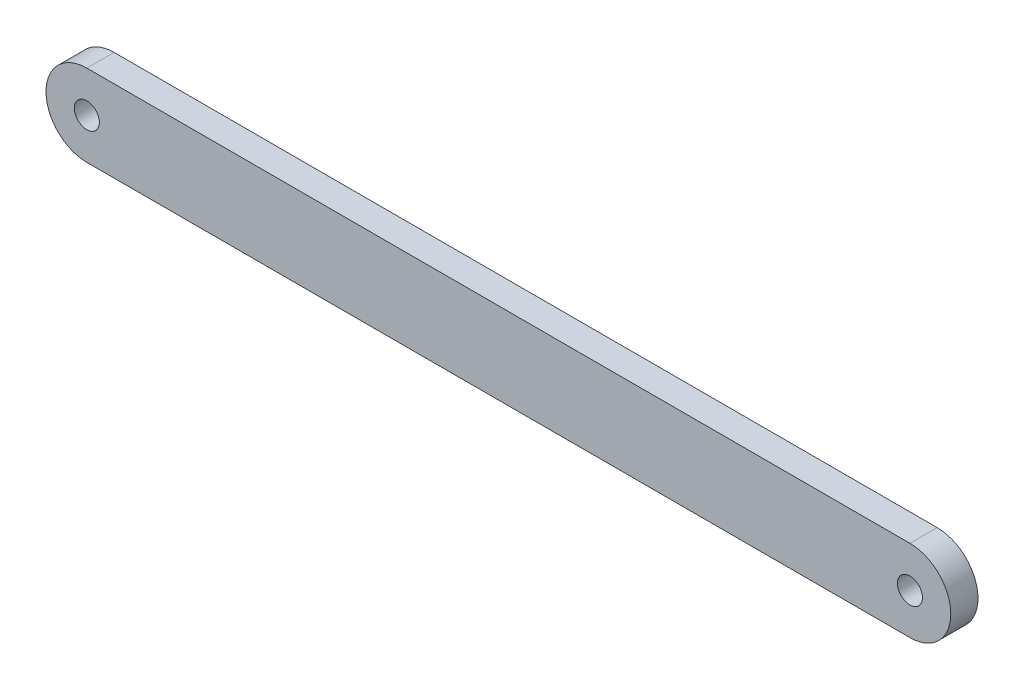
SolidWorks part; units mm, degrees
ref_plane "前视基准面" through (0, 0, 0) normal (0, 0, 1) x (1, 0, 0)
ref_plane "上视基准面" through (0, 0, 0) normal (0, 1, 0) x (1, 0, 0)
ref_plane "右视基准面" through (0, 0, 0) normal (1, 0, 0) x (0, 0, -1)
other "Configuration Table"
sketch "草图1" plane through (0, 0, 0) normal (0, 0, 1) x (1, 0, 0)
  line L1 (-75.6, 7.5) -> (75.6, 7.5)
  line L3 (-75.6, -7.5) -> (75.6, -7.5)
  line L5 (-75.6, 7.5) -> (75.6, -7.5) construction
  line L6 (-75.6, -7.5) -> (75.6, 7.5) construction
  arc A0 (-75.6, 7.5) -> (-75.6, -7.5) centre (-75.6, 0) ccw
  arc A1 (75.6, 7.5) -> (75.6, -7.5) centre (75.6, 0) cw
  circle A2 centre (-75.6, 0) radius 2.3
  circle A3 centre (75.6, 0) radius 2.3
  point P0 (0, 0)
  point P8 (0, 0)
  dimension "D1" = 4.6
  dimension "D2" = 4.6
  dimension "D4" = 15
  dimension "D3" = 151.2
extrude "凸台-拉伸1" add sketch "草图1" along normal blind 5
equation "\"fi\"=4.6"
equation "\"D1@草图1\"=\"fi\""
equation "\"D2@草图1\"=\"fi\""
equation "\"b0\"=75.6"
equation "\"width\"=15"
equation "\"D4@草图1\"=\"width\""
equation "\"depth\"=5"
equation "\"D1@凸台-拉伸1\"=\"depth\""
equation "\"b1\"= \"b0\" * 3 / 2"
equation "\"b2\"= \"b0\" * 6 / 2"
equation "\"b3\"= \"b0\" * 4 / 2"
equation "\"b4\"= \"b0\" * 7 / 2"
equation "\"angle\"= 90度"
equation "\"D3@草图1\"=\"b3\""
